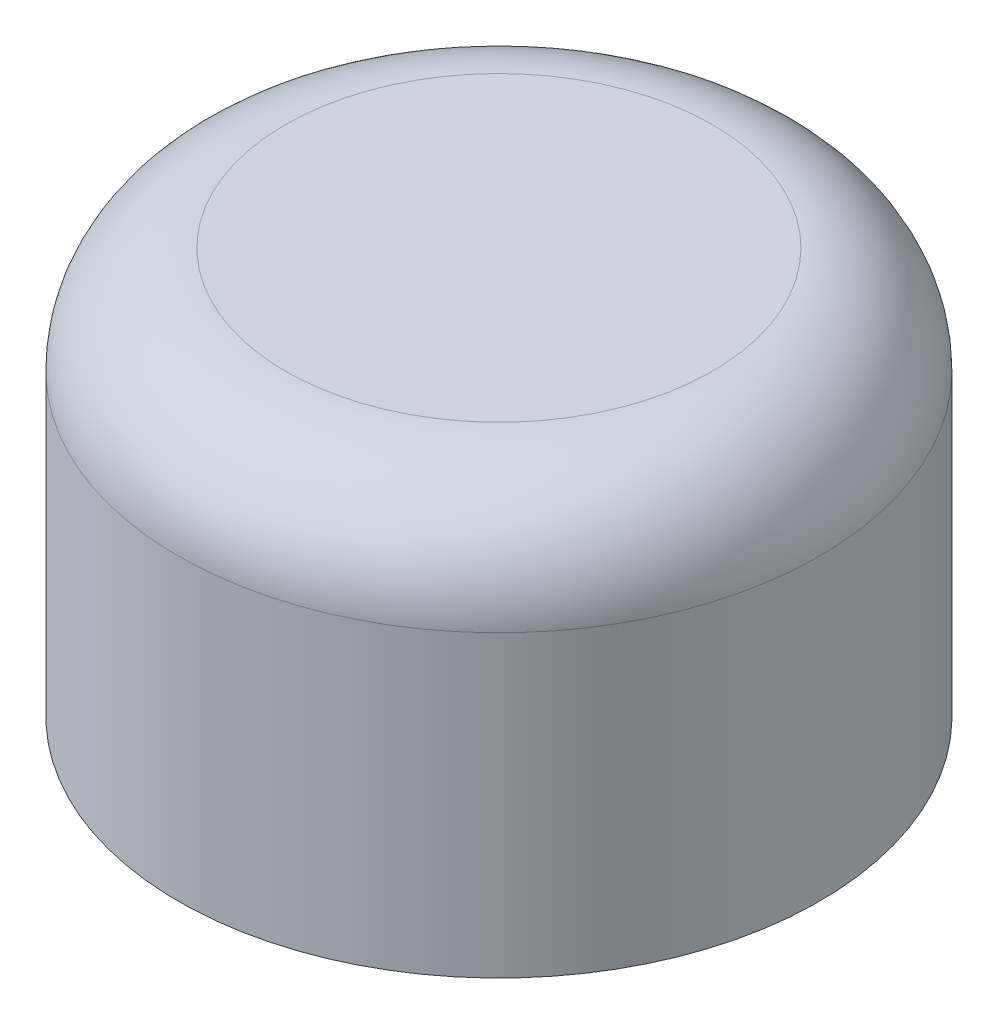
SolidWorks part; units mm, degrees
material "ABS"
ref_plane "正面" through (0, 0, 0) normal (0, 0, 1) x (1, 0, 0)
ref_plane "平面" through (0, 0, 0) normal (0, 1, 0) x (1, 0, 0)
ref_plane "右側面" through (0, 0, 0) normal (1, 0, 0) x (0, 0, -1)
sketch "ｽｹｯﾁ1" plane through (0, 0, 0) normal (0, 0, 1) x (1, 0, 0)
  line L1 (0, 20) -> (10, 20)
  line L3 (15, 15) -> (15, 1)
  line L4 (15, 1) -> (13, 1)
  line L5 (13, 1) -> (13, 3.5)
  line L7 (0, 20) -> (0, 18)
  line L8 (0, 18) -> (10, 18)
  line L9 (13, 3.5) -> (0, 3.5)
  line L10 (0, 3.5) -> (0, 6.5)
  line L11 (0, 6.5) -> (13, 6.5)
  line L12 (13, 6.5) -> (13, 15)
  line L13 (8, 0) -> (8, 4.2574) construction
  arc A0 (10, 20) -> (15, 15) centre (10, 15) cw
  arc A2 (10, 18) -> (13, 15) centre (10, 15) cw
  dimension "D4" = 20
  dimension "D7" = 8
  dimension "D1" = 19
  dimension "D2" = 10
  dimension "D3" = 2
  dimension "D5" = 15
  dimension "D6" = 2
  dimension "D8" = 3.5
  dimension "D9" = 3
revolve "回転1" add sketch "ｽｹｯﾁ1" angle 360 about L10
sketch "ｽｹｯﾁ2" plane through (0, 6.5, 0) normal (0, 1, 0) x (1, 0, 0)
  line L0 (-1, 1) -> (-1, 8)
  line L1 (1, -8) -> (-1, -8)
  line L2 (1, -8) -> (1, -1)
  line L3 (1, 8) -> (-1, 8)
  line L4 (-1, -8) -> (-1, -1)
  line L5 (1, -8) -> (-1, 8) construction
  line L6 (1, 8) -> (-1, -8) construction
  line L7 (-8, 1) -> (-1, 1)
  line L8 (-8, 1) -> (-8, -1)
  line L9 (-8, -1) -> (-1, -1)
  line L10 (8, 1) -> (8, -1)
  line L11 (-8, 1) -> (8, -1) construction
  line L12 (-8, -1) -> (8, 1) construction
  line L13 (1, 1) -> (8, 1)
  line L14 (1, 1) -> (1, 8)
  line L15 (1, -1) -> (8, -1)
  point P0 (0, 0)
  point P5 (0, 0)
  dimension "D1" = 16
  dimension "D2" = 16
  dimension "D3" = 2
  dimension "D4" = 2
extrude "ﾎﾞｽ - 押し出し1" add sketch "ｽｹｯﾁ2" along normal blind 13
